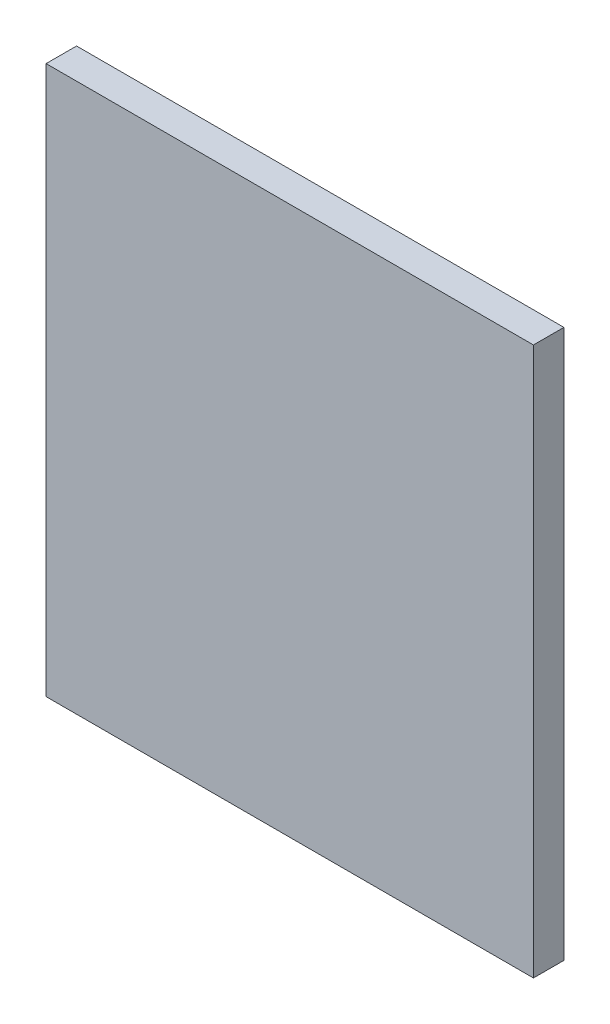
SolidWorks part; units mm, degrees
ref_plane "Front Plane" through (0, 0, 0) normal (0, 0, 1) x (1, 0, 0)
ref_plane "Top Plane" through (0, 0, 0) normal (0, 1, 0) x (1, 0, 0)
ref_plane "Right Plane" through (0, 0, 0) normal (1, 0, 0) x (0, 0, -1)
sketch "Sketch1" plane through (0, 0, 0) normal (0, 0, 1) x (1, 0, 0)
  line L1 (-50.8, -57.15) -> (50.8, -57.15)
  line L2 (-50.8, -57.15) -> (-50.8, 57.15)
  line L3 (-50.8, 57.15) -> (50.8, 57.15)
  line L4 (50.8, -57.15) -> (50.8, 57.15)
  line L5 (-50.8, -57.15) -> (50.8, 57.15) construction
  line L6 (-50.8, 57.15) -> (50.8, -57.15) construction
  point P0 (0, 0)
  dimension "D1" = 114.3
  dimension "D2" = 101.6
extrude "Boss-Extrude1" add sketch "Sketch1" along normal blind 6.35
